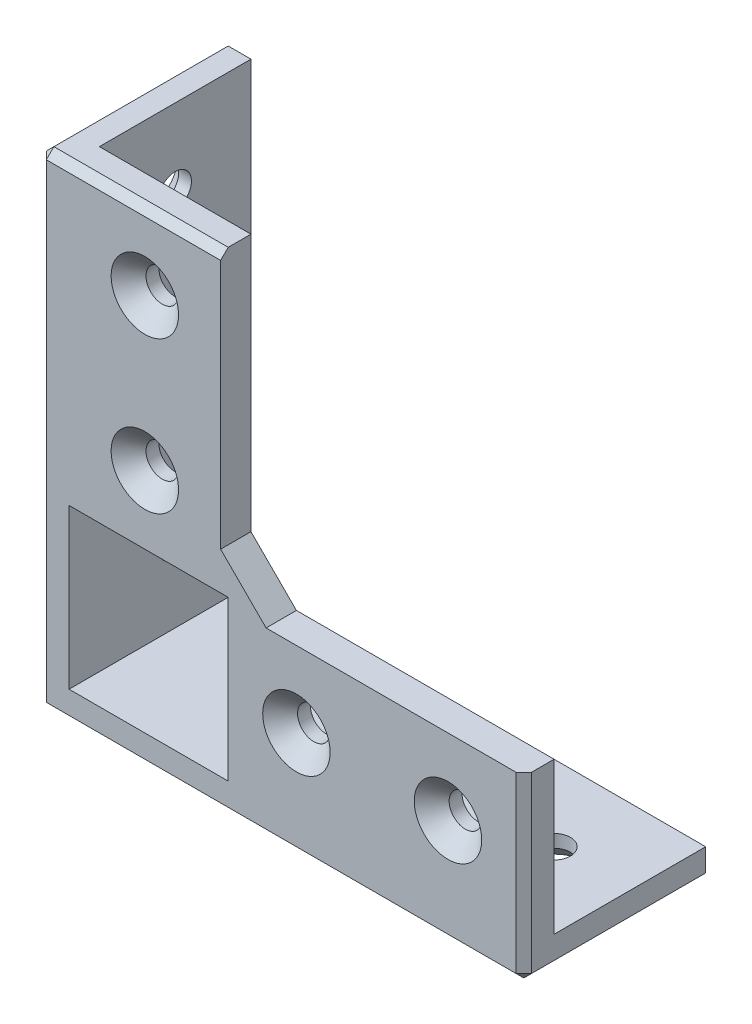
SolidWorks part; units mm, degrees
ref_plane "Front Plane" through (0, 0, 0) normal (0, 0, 1) x (1, 0, 0)
ref_plane "Top Plane" through (0, 0, 0) normal (0, 1, 0) x (1, 0, 0)
ref_plane "Right Plane" through (0, 0, 0) normal (1, 0, 0) x (0, 0, -1)
sketch "Sketch1" plane through (0, 0, 0) normal (0, 0, 1) x (1, 0, 0)
  line L4 (50, -10) -> (50, 10)
  line L5 (50, 10) -> (10, 10)
  line L6 (-10, 0) -> (50, 0) construction
  line L8 (-10, 10) -> (-10, 50)
  line L9 (-10, 50) -> (10, 50)
  line L10 (10, 10) -> (10, 50)
  line L11 (10, 10) -> (-10, 10) construction
  line L12 (-10, 10) -> (-10, -10)
  line L13 (0, 50) -> (0, 0) construction
  line L14 (-10, -10) -> (50, -10)
  circle A0 centre (0, 20) radius 2.15
  circle A1 centre (20, 0) radius 2.15
  circle A3 centre (0, 40) radius 2.15
  circle A4 centre (0, 0) radius 2.15
  circle A5 centre (40, 0) radius 2.15
  point P0 (0, 0)
  point P10 (0, 50)
  dimension "D3" = 4.3
  dimension "D8" = 20
  dimension "D9" = 10
  dimension "D1" = 20
  dimension "D2" = 20
  dimension "D4" = 20
  dimension "D5" = 20
  dimension "D6" = 20
  dimension "D7" = 10
extrude "Boss-Extrude1" add sketch "Sketch1" along normal blind 4
sketch "Sketch2" plane through (0, 0, 0) normal (0, 0, -1) x (-1, 0, 0)
  line L0 (0, 40) -> (0, 20) construction
  line L1 (-40, 0) -> (-20, 0) construction
  line L3 (-2.9, 14) -> (2.9, 14)
  line L4 (-2.9, 14) -> (-2.9, 46)
  line L5 (-2.9, 46) -> (2.9, 46)
  line L6 (2.9, 14) -> (2.9, 46)
  line L7 (-2.9, 14) -> (2.9, 46) construction
  line L8 (-2.9, 46) -> (2.9, 14) construction
  line L9 (-46, -2.9) -> (-14, -2.9)
  line L10 (-46, -2.9) -> (-46, 2.9)
  line L11 (-46, 2.9) -> (-14, 2.9)
  line L12 (-14, -2.9) -> (-14, 2.9)
  line L13 (-46, -2.9) -> (-14, 2.9) construction
  line L14 (-46, 2.9) -> (-14, -2.9) construction
  circle A0 centre (0, 40) radius 2.15 construction
  circle A1 centre (0, 20) radius 2.15 construction
  circle A2 centre (-20, 0) radius 2.15 construction
  circle A3 centre (-40, 0) radius 2.15 construction
  circle A4 centre (0, 40) radius 2.15
  circle A5 centre (0, 20) radius 2.15
  circle A6 centre (-20, 0) radius 2.15
  circle A7 centre (-40, 0) radius 2.15
  point P8 (0, 30)
  point P13 (-30, 0)
  dimension "D1" = 5.8
  dimension "D2" = 6
  dimension "D3" = 6
extrude "Boss-Extrude2" add sketch "Sketch2" along normal blind 0.4
sketch "Sketch3" plane through (0, 0, 4) normal (0, 0, 1) x (1, 0, 0)
  line L0 (-10, 50) -> (-14, 50)
  line L1 (-14, 50) -> (-14, -14)
  line L2 (-14, -14) -> (50, -14)
  line L3 (50, -14) -> (50, -10)
  line L4 (50, -10) -> (-10, -10)
  line L5 (-10, -10) -> (-10, 50)
  dimension "D1" = 4
extrude "Boss-Extrude4" add sketch "Sketch3" against normal blind 24
sketch "Sketch4" plane through (-14, 0, 0) normal (-1, 0, 0) x (0, 0, 1)
  line L0 (-10, 50) -> (-10, -14) construction
  line L1 (-20, 50) -> (4, 50) construction
  line L2 (-20, -14) -> (4, -14) construction
  line L3 (-20, 50) -> (-20, -14) construction
  line L4 (-0.4, 42.15) -> (-0.4, 37.85) construction
  line L5 (-0.4, 22.15) -> (-0.4, 17.85) construction
  line L7 (0, 2.15) -> (0, -2.15) construction
  line L16 (0, 2.15) -> (0, -2.15) construction
  line L17 (-0.4, 22.15) -> (-0.4, 17.85) construction
  line L18 (-0.4, 42.15) -> (-0.4, 37.85) construction
  line L19 (-10, 20) -> (-0.4, 20) construction
  line L20 (0, 0) -> (-10, 0) construction
  circle A0 centre (-10, 40) radius 2.15
  circle A1 centre (-10, 20) radius 2.15
  circle A2 centre (-10, 0) radius 2.15
  point P20 (-0.4, 40)
  dimension "D2" = 4.3
  dimension "D1" = 10
extrude "Cut-Extrude1" cut sketch "Sketch4" against normal up to surface (4 mm away) up to face at (-10, 20, -10)
sketch "Sketch5" plane through (0, -14, 0) normal (0, -1, 0) x (1, 0, 0)
  line L0 (-14, -10) -> (50, -10) construction
  line L1 (-14, -20) -> (-14, 4) construction
  line L2 (50, -20) -> (50, 4) construction
  line L3 (-14, -20) -> (50, -20) construction
  line L4 (37.85, -0.4) -> (42.15, -0.4) construction
  line L5 (17.85, -0.4) -> (22.15, -0.4) construction
  line L6 (-2.15, 0) -> (2.15, 0) construction
  line L7 (37.85, -0.4) -> (42.15, -0.4) construction
  line L8 (17.85, -0.4) -> (22.15, -0.4) construction
  line L9 (-2.15, 0) -> (2.15, 0) construction
  line L10 (40, -0.4) -> (40, -10) construction
  line L12 (20, -0.4) -> (20, -10) construction
  line L13 (0, 0) -> (0, -10) construction
  circle A0 centre (40, -10) radius 2.15
  circle A1 centre (20, -10) radius 2.15
  circle A2 centre (0, -10) radius 2.15
  dimension "D2" = 4.3
  dimension "D1" = 10
extrude "Cut-Extrude2" cut sketch "Sketch5" against normal through all
chamfer "Chamfer2" distance 2.3 angle 45 11 edges at (22.15, 0, 4) (42.15, 0, 4) (2.15, 0, 4) (2.15, 20, 4) (2.15, 40, 4) (-14, 37.85, -10) (-14, 17.85, -10) (-14, -2.15, -10) (0, -14, -12.15) (20, -14, -12.15) (40, -14, -12.15)
chamfer "Chamfer3" distance 1 angle 45 9 edges at (-2, 50, 4) (50, -2, 4) (50, -14, -8) (-14, 50, -8) (-14, 18, 4) (18, -14, 4) (-14, -14, -8) (-14, 18, -20) (18, -14, -20)
sketch "Sketch7" plane through (0, 0, 4) normal (0, 0, 1) x (1, 0, 0)
  line L0 (10, 10) -> (10, 16)
  line L1 (10, 10) -> (10, 49) construction
  line L2 (10, 16) -> (16, 10)
  line L3 (49, 10) -> (10, 10) construction
  line L4 (16, 10) -> (10, 10)
  dimension "D1" = 6
extrude "Boss-Extrude5" add sketch "Sketch7" against normal up to surface (4 mm away) up to face at (0, 30, 0)
sketch "Sketch6" plane through (0, 0, 4) normal (0, 0, 1) x (1, 0, 0)
  line L0 (-10, 10) -> (-10, 11)
  line L1 (-10, -10) -> (10, -10)
  line L2 (-10, -10) -> (-10, 10)
  line L3 (-10, 10) -> (10, 10) construction
  line L4 (10, -10) -> (10, 10) construction
  line L5 (-10, -10) -> (10, 10) construction
  line L6 (-10, 10) -> (10, -10) construction
  line L7 (-10, 11) -> (11, 11)
  line L8 (11, 11) -> (11, -10)
  line L9 (11, -10) -> (10, -10)
  point P0 (0, 0)
  dimension "D1" = 20
  dimension "D2" = 1
extrude "Cut-Extrude5" cut sketch "Sketch6" against normal up to surface (4 mm away) up to face at (16.5714, 16.5714, 0)
sketch "Sketch8" plane through (0, 0, 0) normal (0, 0, -1) x (-1, 0, 0)
  line L1 (10, 50) -> (-50, 50)
  line L2 (10, 50) -> (10, -10)
  line L3 (10, -10) -> (-50, -10)
  line L4 (-50, 50) -> (-50, -10)
extrude "Cut-Extrude6" cut sketch "Sketch8" along normal through all
